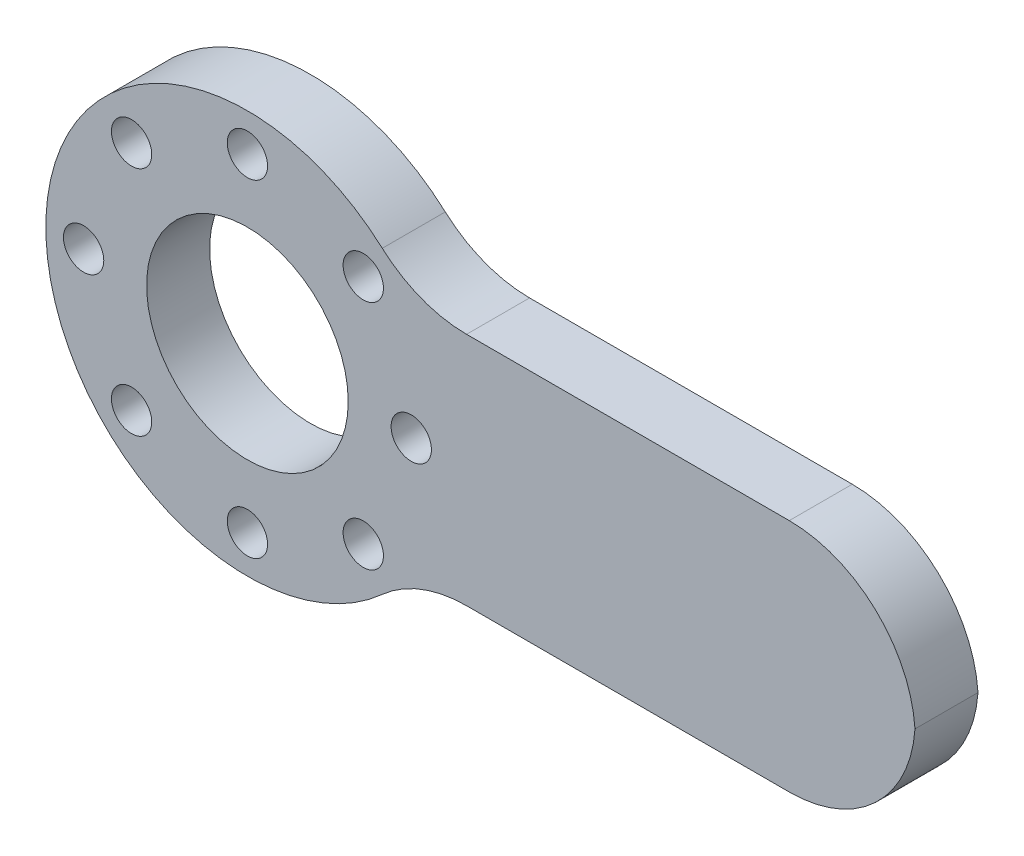
SolidWorks part; units mm, degrees
ref_plane "Front Plane" through (0, 0, 0) normal (0, 0, 1) x (1, 0, 0)
ref_plane "Top Plane" through (0, 0, 0) normal (0, 1, 0) x (1, 0, 0)
ref_plane "Right Plane" through (0, 0, 0) normal (1, 0, 0) x (0, 0, -1)
sketch "Sketch1" plane through (0, 0, 0) normal (0, 0, 1) x (1, 0, 0)
  line L0 (0, 0) -> (13, 0) construction
  line L1 (0, 13) -> (-9.1924, 9.1924) construction
  line L2 (-9.1924, 9.1924) -> (-13, 0) construction
  line L3 (-13, 0) -> (-9.1924, -9.1924) construction
  line L4 (-9.1924, -9.1924) -> (0, -13) construction
  line L5 (0, -13) -> (9.1924, -9.1924) construction
  line L6 (9.1924, -9.1924) -> (13, 0) construction
  line L7 (13, 0) -> (9.1924, 9.1924) construction
  line L8 (9.1924, 9.1924) -> (0, 13) construction
  line L9 (13, 0) -> (13, 9.3274) construction
  line L10 (13, 0) -> (13, -9.3274) construction
  line L11 (13, 9.3274) -> (53, 9.3274)
  line L12 (13, -9.3274) -> (53, -9.3274)
  line L13 (53, 9.3274) -> (53, -9.3274)
  arc A0 (13, 9.3274) -> (13, -9.3274) centre (0, 0) ccw
  circle A1 centre (0, 0) radius 13 construction
  circle A2 centre (0, 13) radius 1.6
  circle A3 centre (9.1924, 9.1924) radius 1.6
  circle A4 centre (13, 0) radius 1.6
  circle A5 centre (9.1924, -9.1924) radius 1.6
  circle A6 centre (0, -13) radius 1.6
  circle A7 centre (-9.1924, -9.1924) radius 1.6
  circle A8 centre (-13, 0) radius 1.6
  circle A9 centre (-9.1924, 9.1924) radius 1.6
  circle A10 centre (0, 0) radius 8
  point P29 (0, 0)
  dimension "D1" = 32
  dimension "D2" = 26
  dimension "D3" = 3.2
  dimension "D5" = 16
  dimension "D6" = 40
  dimension "D4" = 8
extrude "Boss-Extrude1" add sketch "Sketch1" along normal blind 5
fillet "Fillet1" radius 10 2 edges at (53, -9.3274, 2.5) (53, 9.3274, 2.5)
fillet "Fillet2" radius 10 2 edges at (13, -9.3274, 2.5) (13, 9.3274, 2.5)
